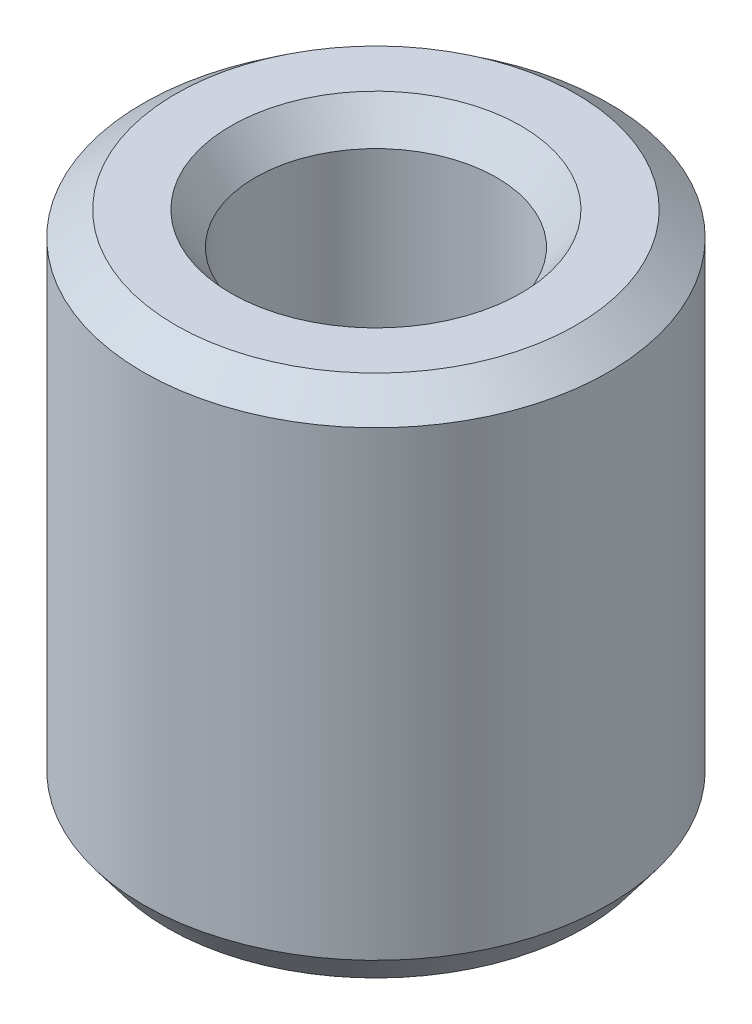
SolidWorks part; units mm, degrees
ref_plane "Front Plane" through (0, 0, 0) normal (0, 0, 1) x (1, 0, 0)
ref_plane "Top Plane" through (0, 0, 0) normal (0, 1, 0) x (1, 0, 0)
ref_plane "Right Plane" through (0, 0, 0) normal (1, 0, 0) x (0, 0, -1)
sketch "Sketch1" plane through (0, 0, 0) normal (0, 1, 0) x (1, 0, 0)
  circle A0 centre (0, 0) radius 5
  dimension "SLEEVE_OD" = 10
extrude "Boss-Extrude1" add sketch "Sketch1" along normal blind 11.1278
sketch "Sketch2" plane through (0, 0, 0) normal (0, 1, 0) x (1, 0, 0)
  circle A0 centre (0, 0) radius 2.5906
  dimension "BORE_D" = 5.1811
extrude "Cut-Extrude1" cut sketch "Sketch2" along normal through all
chamfer "Chamfer1" distance 0.5239 angle 53.118 4 edges at (0, 11.1278, 2.5906) (0, 0, 2.5906) (0, 0, 5) (0, 11.1278, 5) first distance on face at (0, 11.1278, 2.5906) first distance on face at (0, 0, 2.5906) first distance on face at (0, 11.1278, 5)
